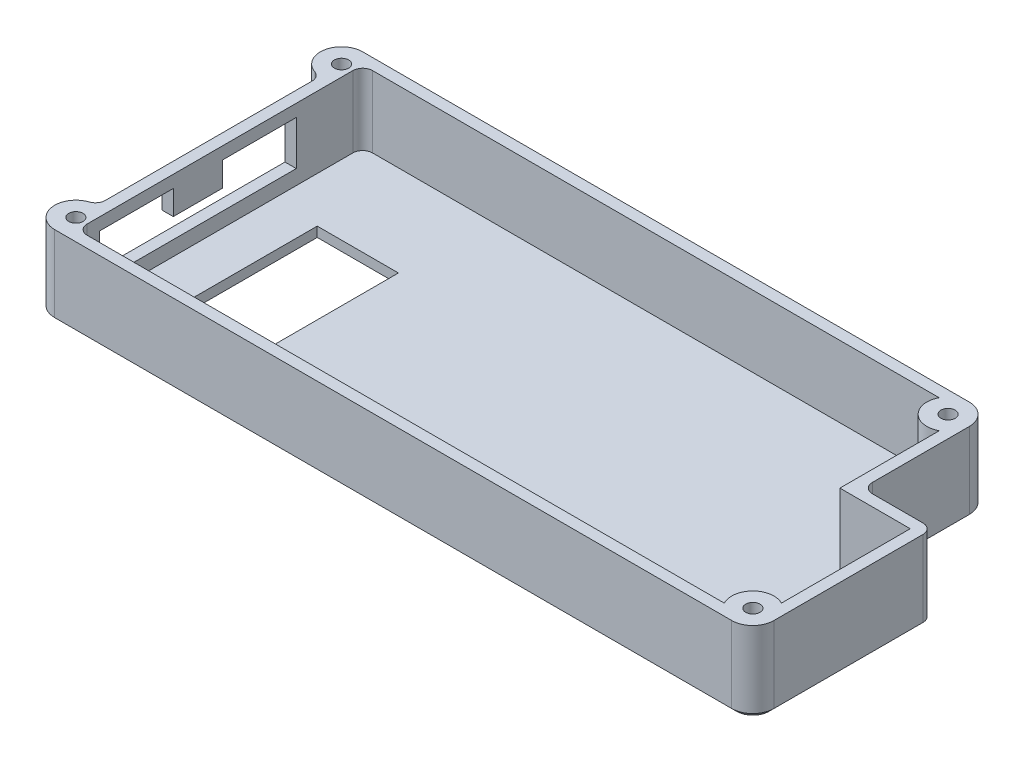
SolidWorks part; units mm, degrees
ref_plane "Front Plane" through (0, 0, 0) normal (0, 0, 1) x (1, 0, 0)
ref_plane "Top Plane" through (0, 0, 0) normal (0, 1, 0) x (1, 0, 0)
ref_plane "Right Plane" through (0, 0, 0) normal (1, 0, 0) x (0, 0, -1)
sketch "Sketch1" plane through (0, 0, 0) normal (0, 1, 0) x (1, 0, 0)
  line L0 (-71.5618, 3.106) -> (49.4382, 3.106) construction
  line L1 (-71.5618, 31.106) -> (49.4382, 31.106)
  line L2 (-71.5618, 31.106) -> (-71.5618, -24.894)
  line L3 (-71.5618, -24.894) -> (49.4382, -24.894)
  line L4 (49.4382, 31.106) -> (49.4382, -24.894)
  line L5 (-60.6618, -24.894) -> (-60.6618, -31.6828) construction
  line L6 (-68.0618, 27.606) -> (-10.0618, 27.606)
  line L7 (-68.0618, 27.606) -> (-68.0618, -21.394)
  line L8 (-68.0618, -21.394) -> (-10.0618, -21.394)
  line L9 (-10.0618, 27.606) -> (-10.0618, -21.394)
  line L10 (-39.5618, -24.894) -> (-39.5618, -31.6828) construction
  line L11 (-18.0618, -24.894) -> (-18.0618, -31.6828) construction
  line L12 (-65.4118, -26.5648) -> (-55.9118, -26.5648) construction
  line L13 (-48.0618, -26.5648) -> (-31.0618, -26.5648) construction
  line L14 (-22.0618, -26.5648) -> (-14.0618, -26.5648) construction
  line L15 (-72.5618, 9.606) -> (-72.5618, -3.394) construction
  line L16 (-71.5618, 3.106) -> (-72.5618, 3.106) construction
  dimension "D1" = 121
  dimension "D2" = 56
  dimension "D3" = 49
  dimension "D4" = 58
  dimension "D5" = 3.5
  dimension "D6" = 3.5
  dimension "D7" = 10.9
  dimension "D8" = 32
  dimension "D9" = 53.5
  dimension "D10" = 2
  dimension "D11" = 13
  dimension "D12" = 9.5
  dimension "D13" = 17
  dimension "D14" = 8
sketch "Sketch3" plane through (0, 0, 0) normal (0, 1, 0) x (1, 0, 0)
  line L0 (55.0382, -25.894) -> (64.7382, -25.894)
  line L1 (52.7382, 8.406) -> (67.0382, 8.406)
  line L2 (55.0382, 6.106) -> (64.7382, 6.106) construction
  line L3 (52.7382, -28.194) -> (67.0382, -28.194)
  line L4 (52.7382, 34.406) -> (-74.8618, 34.406)
  line L5 (-74.8618, 34.406) -> (-74.8618, -28.194)
  line L6 (-74.8618, -28.194) -> (52.7382, -28.194)
  line L7 (52.7382, 8.406) -> (52.7382, 34.406)
  line L8 (50.4382, 32.106) -> (-72.5618, 32.106)
  line L9 (50.4382, -25.894) -> (50.4382, 32.106)
  line L10 (-72.5618, -25.894) -> (50.4382, -25.894)
  line L11 (-72.5618, 32.106) -> (-72.5618, -25.894)
  line L12 (50.4382, 32.106) -> (-72.5618, 32.106)
  line L13 (50.4382, 6.106) -> (50.4382, 32.106)
  line L14 (-72.5618, -25.894) -> (50.4382, -25.894)
  line L15 (-72.5618, 32.106) -> (-72.5618, -25.894)
  line L16 (-11.0618, 3.106) -> (-11.0618, 34.406) construction
  line L17 (-71.5618, 3.106) -> (49.4382, 3.106) construction
  line L18 (67.0382, 8.406) -> (67.0382, -28.194)
  line L19 (64.7382, 6.106) -> (64.7382, -25.894)
  line L20 (-74.8618, 3.106) -> (52.7382, 3.106) construction
  line L21 (50.4382, 6.106) -> (64.7382, 6.106)
  line L22 (55.0382, -25.894) -> (50.4382, -25.894)
  line L23 (55.0382, 6.106) -> (55.0382, -25.894) construction
  line L24 (52.7382, 8.406) -> (52.7382, -28.194) construction
  line L25 (52.7382, -28.194) -> (52.7382, 34.406) construction
  line L26 (50.4382, -25.894) -> (50.4382, 32.106) construction
  dimension "D3" = 2.3
  dimension "D4" = 26
  dimension "D5" = 12
  dimension "D1" = 1
  dimension "D2" = 2.3
extrude "Boss-Extrude1" add sketch "Sketch3" along normal blind 16.5
sketch "Sketch5" plane through (0, 0, 0) normal (0, 1, 0) x (1, 0, 0)
  line L1 (-72.5618, 32.106) -> (50.4382, 32.106)
  line L2 (-72.5618, 32.106) -> (-72.5618, -25.894)
  line L3 (-72.5618, -25.894) -> (50.4382, -25.894)
  line L4 (50.4382, 32.106) -> (50.4382, 6.106)
  line L5 (50.4382, 6.106) -> (64.7382, 6.106)
  line L7 (50.4382, -25.894) -> (64.7382, -25.894)
  line L8 (64.7382, 6.106) -> (64.7382, -25.894)
extrude "Boss-Extrude2" add sketch "Sketch5" along normal blind 2
fillet "Fillet6" radius 2 1 edges at (50.4382, 9.25, -32.106)
fillet "Fillet8" radius 2 2 edges at (-72.5618, 9.25, 25.894) (-72.5618, 9.25, -32.106)
sketch "Sketch17" plane through (0, 0, 0) normal (0, 1, 0) x (1, 0, 0)
  line L0 (-74.8618, 34.406) -> (-74.8618, -28.194) construction
  line L1 (-74.8618, 34.406) -> (-74.8618, 25.806)
  line L2 (-74.8618, 25.806) -> (-74.659, 25.9406)
  line L3 (-74.8618, -19.594) -> (-74.8618, -28.194)
  line L4 (-74.8618, -28.194) -> (-74.659, -28.0594)
  arc A0 (-74.8618, -19.594) -> (-74.8618, -28.194) centre (-74.8618, -23.894) ccw
  arc A1 (-74.8618, 34.406) -> (-74.8618, 25.806) centre (-74.8618, 30.106) ccw
extrude "Boss-Extrude6" add sketch "Sketch17" along normal up to vertex (16.5 mm away) contours L1 A1 | L3 A0 up to point (-74.8618, 16.5, -34.406)
hole_wizard "Ø2.9 (2.9) Diameter Hole2" positions "Sketch19" profile "Sketch18" hole size "Ø2.9" standard "ANSI Metric" end condition up to next
sketch "Sketch19" plane through (0, 16.5, 0) normal (0, 1, 0) x (1, 0, 0)
  point P0 (-74.8618, 30.106)
sketch "Sketch18" plane through (-74.8618, 16.5, -30.106) normal (1, 0, 0) x (0, 0, 1)
  line L0 (0, 0) -> (0, 16.5)
  line L1 (0, 16.5) -> (1.45, 16.5)
  line L2 (1.45, 16.5) -> (1.45, 0)
  line L5 (1.45, 0) -> (0, 0)
  line L11 (0, -6.35) -> (0, 107.95) construction
  dimension "Thru Hole Dia." = 2.9
  dimension "Thru Hole Depth" = 16.5
hole_wizard "Ø2.9 (2.9) Diameter Hole1" positions "Sketch21" profile "Sketch20" hole size "Ø2.9" standard "ANSI Metric" end condition up to next
sketch "Sketch21" plane through (0, 16.5, 0) normal (0, 1, 0) x (1, 0, 0)
  point P0 (-74.8618, -23.894)
sketch "Sketch20" plane through (-74.8618, 16.5, 23.894) normal (1, 0, 0) x (0, 0, 1)
  line L0 (0, 0) -> (0, 16.5)
  line L1 (0, 16.5) -> (1.45, 16.5)
  line L2 (1.45, 16.5) -> (1.45, 0)
  line L5 (1.45, 0) -> (0, 0)
  line L11 (0, -6.35) -> (0, 107.95) construction
  dimension "Thru Hole Dia." = 2.9
  dimension "Thru Hole Depth" = 16.5
sketch "Sketch24" plane through (0, 2, 0) normal (0, 1, 0) x (1, 0, 0)
  circle A0 centre (62.7384, -23.8858) radius 4.3
  circle A1 centre (48.4185, 30.106) radius 4.3
extrude "Boss-Extrude7" add sketch "Sketch24" along normal up to surface (14.5 mm away) up to face at (-74.8618, 16.5, 25.344)
hole_wizard "Ø2.9 (2.9) Diameter Hole3" positions "Sketch26" profile "Sketch25" hole size "Ø2.9" standard "ANSI Metric" end condition up to next
sketch "Sketch26" plane through (0, 16.5, 0) normal (0, 1, 0) x (1, 0, 0)
  point P0 (62.7384, -23.8858)
sketch "Sketch25" plane through (62.7384, 16.5, 23.8858) normal (1, 0, 0) x (0, 0, 1)
  line L0 (0, 0) -> (0, 16.5)
  line L1 (0, 16.5) -> (1.45, 16.5)
  line L2 (1.45, 16.5) -> (1.45, 0)
  line L5 (1.45, 0) -> (0, 0)
  line L11 (0, -6.35) -> (0, 107.95) construction
  dimension "Thru Hole Dia." = 2.9
  dimension "Thru Hole Depth" = 16.5
hole_wizard "Ø2.9 (2.9) Diameter Hole4" positions "Sketch28" profile "Sketch27" hole size "Ø2.9" standard "ANSI Metric" end condition up to next
sketch "Sketch28" plane through (0, 16.5, 0) normal (0, 1, 0) x (1, 0, 0)
  point P0 (48.4185, 30.106)
sketch "Sketch27" plane through (48.4185, 16.5, -30.106) normal (1, 0, 0) x (0, 0, 1)
  line L0 (0, 0) -> (0, 16.5)
  line L1 (0, 16.5) -> (1.45, 16.5)
  line L2 (1.45, 16.5) -> (1.45, 0)
  line L5 (1.45, 0) -> (0, 0)
  line L11 (0, -6.35) -> (0, 107.95) construction
  dimension "Thru Hole Dia." = 2.9
  dimension "Thru Hole Depth" = 16.5
fillet "Fillet10" radius 4.3 1 edges at (52.7382, 8.25, -34.406)
fillet "Fillet16" radius 4.3 1 edges at (67.0382, 8.25, 28.194)
fillet "Fillet17" radius 2 2 edges at (52.7382, 8.25, -8.406) (67.0382, 8.25, -8.406)
fillet "Fillet18" radius 2 2 edges at (-74.8618, 8.25, 19.594) (-74.8618, 8.25, -25.806)
chamfer "Chamfer5" distance 1 angle 45 14 edges at (-79.1058, 0, 24.5855) (-6.0618, 0, 28.194) (-75.2385, 0, 19.0883) (65.7788, 0, 26.9346) (-74.8618, 0, -3.106) (67.0382, 0, 8.744) (-75.2385, 0, -25.3002) (66.4524, 0, -7.8202) (-79.1058, 0, -30.7975) (59.8882, 0, -8.406) (-13.2118, 0, -34.406) (53.324, 0, -8.9918) (51.4788, 0, -33.1466) (52.7382, 0, -20.256)
sketch "Sketch29" plane through (0, 2, 0) normal (0, 1, 0) x (1, 0, 0)
  line L1 (-72.6036, 31.806) -> (-46.2036, 31.806)
  line L2 (-72.6036, 31.806) -> (-72.6036, -25.594)
  line L3 (-72.6036, -25.594) -> (-46.2036, -25.594)
  line L4 (-46.2036, 31.806) -> (-46.2036, -25.594)
  line L5 (-63.3036, 13.606) -> (-46.8036, 13.606)
  line L6 (-63.3036, 13.606) -> (-63.3036, -14.894)
  line L7 (-63.3036, -14.894) -> (-46.8036, -14.894)
  line L8 (-46.8036, 13.606) -> (-46.8036, -14.894)
  line L9 (-72.6036, 3.906) -> (-70.1072, 3.906)
  line L10 (-72.6036, 3.906) -> (-72.6036, -4.594)
  line L11 (-72.6036, -4.594) -> (-70.1072, -4.594)
  line L12 (-70.1072, 3.906) -> (-70.1072, -4.594)
  dimension "D1" = 57.4
  dimension "D2" = 26.4
  dimension "D3" = 9.3
  dimension "D4" = 16.5
  dimension "D5" = 28.5
  dimension "D6" = 10.7
  dimension "D7" = 21
  dimension "D8" = 8.5
extrude "Cut-Extrude1" cut sketch "Sketch29" against normal blind 10 contours L8 L5 L6 L7
sketch "Sketch30" plane through (-74.8618, 0, 0) normal (-1, 0, 0) x (0, 0, 1)
  line L0 (17.9199, 0) -> (-24.1319, 0) construction
  line L1 (-3.606, 9.042) -> (6.394, 9.042)
  line L3 (-3.606, 5) -> (6.394, 5)
  line L6 (-3.606, 5) -> (-18.606, 5)
  line L7 (-3.606, 5) -> (-3.606, 14)
  line L8 (-3.606, 14) -> (-18.606, 14)
  line L9 (-18.606, 5) -> (-18.606, 14)
  line L10 (6.394, 5) -> (21.394, 5)
  line L11 (6.394, 5) -> (6.394, 14)
  line L12 (6.394, 14) -> (21.394, 14)
  line L13 (21.394, 5) -> (21.394, 14)
  dimension "D1" = 5
  dimension "D3" = 9
  dimension "D4" = 9
  dimension "D5" = 15
  dimension "D6" = 15
  dimension "D7" = 4.5
extrude "Cut-Extrude2" cut sketch "Sketch30" against normal up to next and the other way through all
